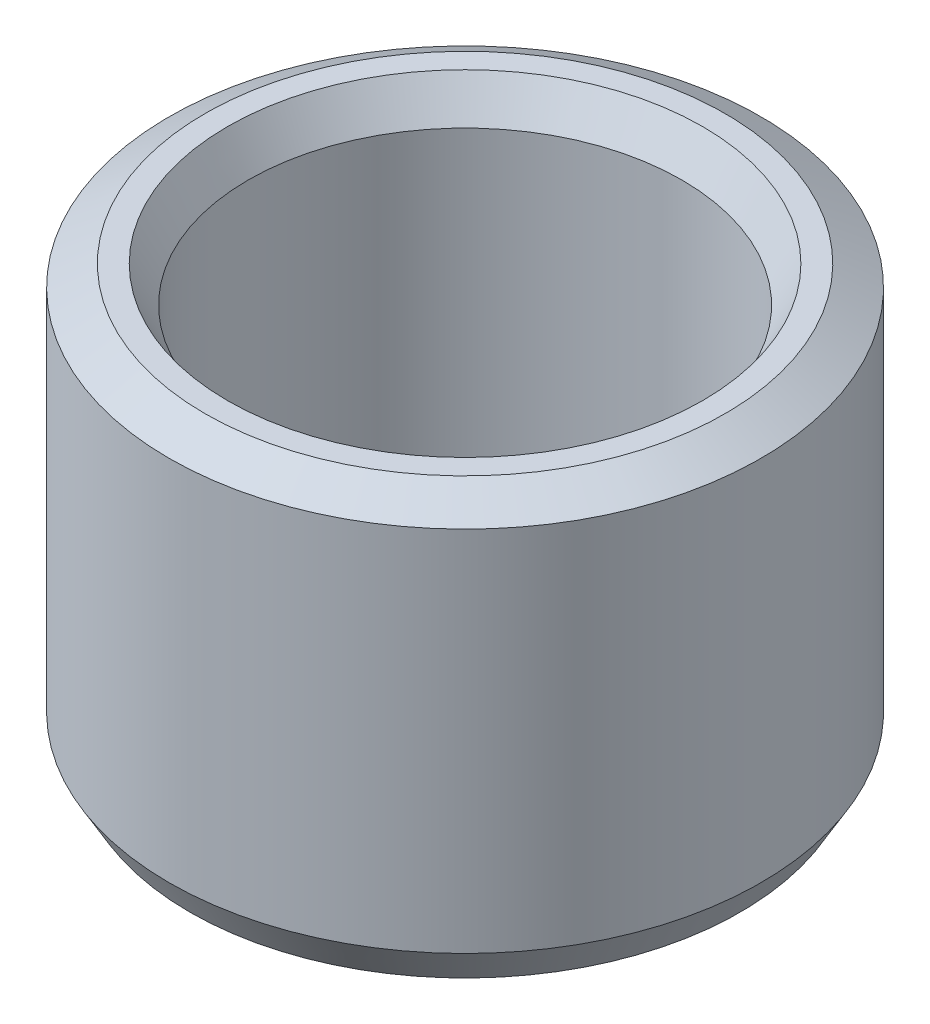
SolidWorks part; units mm, degrees
ref_plane "Front Plane" through (0, 0, 0) normal (0, 0, 1) x (1, 0, 0)
ref_plane "Top Plane" through (0, 0, 0) normal (0, 1, 0) x (1, 0, 0)
ref_plane "Right Plane" through (0, 0, 0) normal (1, 0, 0) x (0, 0, -1)
sketch "Sketch1" plane through (0, 0, 0) normal (0, 1, 0) x (1, 0, 0)
  circle A0 centre (0, 0) radius 52.5
  dimension "SLEEVE_OD" = 105
extrude "Boss-Extrude1" add sketch "Sketch1" along normal blind 75.2497
sketch "Sketch2" plane through (0, 0, 0) normal (0, 1, 0) x (1, 0, 0)
  circle A0 centre (0, 0) radius 38.4566
  dimension "BORE_D" = 76.9133
extrude "Cut-Extrude1" cut sketch "Sketch2" along normal through all
chamfer "Chamfer1" distance 3.6763 angle 60 4 edges at (0, 75.2497, 38.4566) (0, 0, 38.4566) (0, 0, 52.5) (0, 75.2497, 52.5) first distance on face at (0, 75.2497, 38.4566) first distance on face at (0, 0, 38.4566) first distance on face at (0, 75.2497, 52.5)
